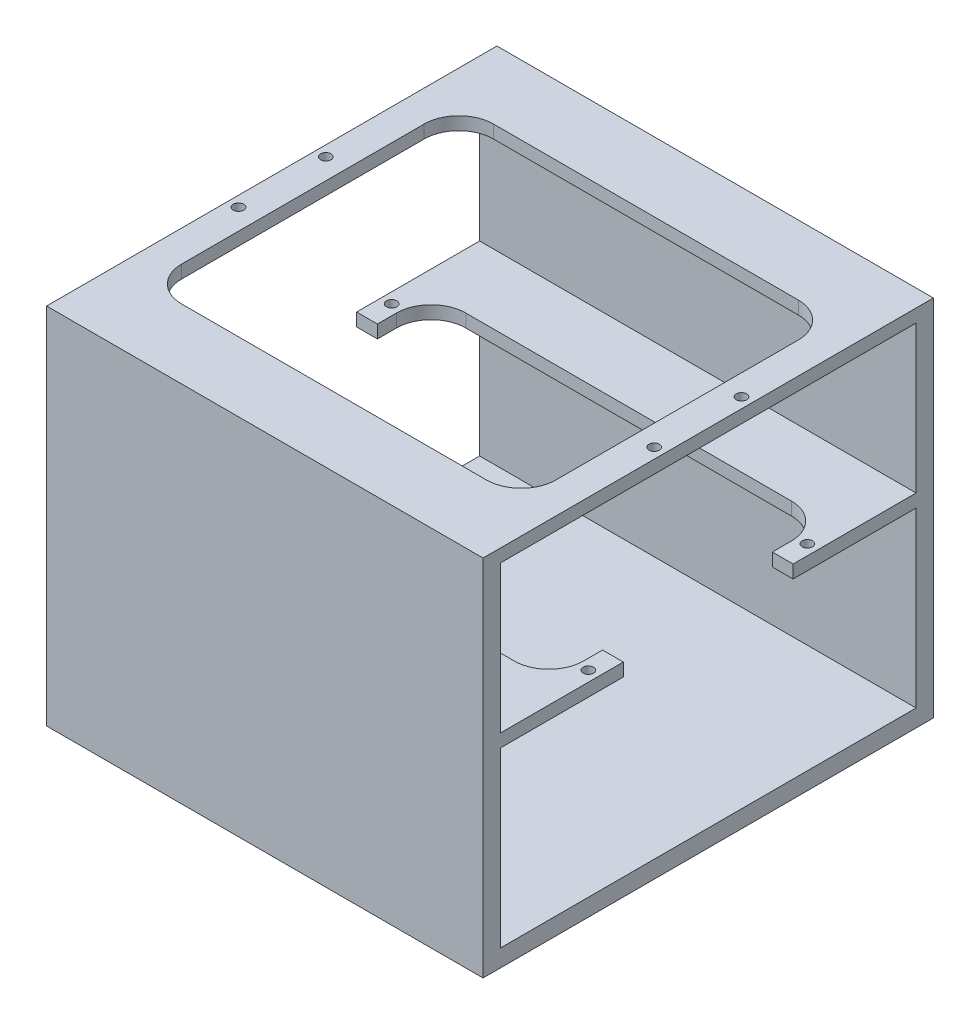
SolidWorks part; units mm, degrees
ref_plane "Front Plane" through (0, 0, 0) normal (0, 0, 1) x (1, 0, 0)
ref_plane "Top Plane" through (0, 0, 0) normal (0, 1, 0) x (1, 0, 0)
ref_plane "Right Plane" through (0, 0, 0) normal (1, 0, 0) x (0, 0, -1)
sketch "Sketch1" plane through (0, 0, 0) normal (1, 0, 0) x (0, 0, -1)
  line L0 (-95, 46.4295) -> (-95, -3.5705)
  line L1 (-43.5, 92.6795) -> (-95, 92.6795)
  line L3 (-43.5, 96.4295) -> (-100, 96.4295)
  line L4 (-100, 86.4295) -> (-100, 96.4295)
  line L5 (-100, 96.4295) -> (-90, 96.4295)
  line L6 (-100, 96.4295) -> (-100, -8.5705)
  line L7 (-100, -8.5705) -> (-90, -8.5705)
  line L8 (-95, 92.6795) -> (-95, 50.1795)
  line L9 (-95, 50.1795) -> (-59.5, 50.1795)
  line L11 (-95, 46.4295) -> (-59.5, 46.4295)
  line L12 (-59.5, 50.1795) -> (-59.5, 46.4295)
  line L13 (-90, -8.5705) -> (-35, -8.5705)
  line L15 (-95, -3.5705) -> (-35, -3.5705)
  line L16 (-35, -8.5705) -> (-35, -3.5705)
  line L18 (-43.5, 96.4295) -> (-35, 96.4295)
  line L20 (-43.5, 92.6795) -> (-35, 92.6795)
  line L21 (-35, 96.4295) -> (-35, 92.6795)
  dimension "D1" = 3.75
  dimension "D2" = 56.5
  dimension "D3" = 5
  dimension "D4" = 105
  dimension "D5" = 55
  dimension "D6" = 3.75
  dimension "D8" = 5
  dimension "D9" = 65
extrude "Boss-Extrude1" add sketch "Sketch1" along normal blind 126 contours L13 L16 L15 L0 L11 L12 L9 L8 L1 L3 L4 L6 L7 region at (0, 21.4295, 96.2349)
sketch "Sketch2" plane through (0, 96.4295, 0) normal (0, 1, 0) x (1, 0, 0)
  line L0 (0, -35.75) -> (0, 35.75) construction
  line L1 (126, -35) -> (0, -35) construction
  circle A0 centre (3, -47.6) radius 1.5
  circle A1 centre (123, -47.6) radius 1.5
  point P6 (123, -48)
  dimension "D1" = 3
  dimension "D2" = 3
  dimension "D3" = 120
  dimension "D4" = 3
  dimension "D5" = 12.6
extrude "Cut-Extrude1" cut sketch "Sketch2" against normal up to surface (46.25 mm away) contours A1 | A0 up to face at (63, 50.1795, 77.25)
sketch "Sketch3" plane through (0, 50.1795, 0) normal (0, 1, 0) x (1, 0, 0)
  line L3 (126, -35) -> (126, -100) construction
  line L4 (0, -35.75) -> (0, 35.75) construction
  line L5 (126, -35) -> (0, -35) construction
  line L7 (6, -95) -> (6, -59.5)
  line L8 (6, -65) -> (6, -35)
  line L9 (16, -75) -> (110, -75)
  line L10 (120, -95) -> (120, -59.5)
  line L11 (120, -65) -> (120, -35)
  line L12 (6, -35) -> (120, -35)
  circle A0 centre (3, -66.6) radius 1.5
  circle A1 centre (123, -66.6) radius 1.5
  arc A3 (16, -75) -> (6, -65) centre (16, -65) cw
  arc A4 (110, -75) -> (120, -65) centre (110, -65) ccw
  circle A8 centre (3, -47.6) radius 1.5 construction
  point P4 (3, -47.2759)
  point P5 (123.0848, -60.1289)
  point P6 (97.4811, -22.7665)
  point P7 (130.4814, -52.7323)
  point P8 (0, 0)
  point P9 (3, -48)
  point P25 (122.9283, -48)
  point P28 (0, 0)
  point P29 (2.7505, -62.7572)
  dimension "D1" = 3
  dimension "D2" = 3
  dimension "D4" = 3
  dimension "D5" = 19
  dimension "D8" = 10
  dimension "D9" = 10
  dimension "D3" = 3
  dimension "D6" = 6
  dimension "D10" = 40
  dimension "D7" = 6
extrude "Cut-Extrude3" cut sketch "Sketch3" against normal up to surface (53.75 mm away) contours A0 | A1 | L11 L12 L8 A3 L9 A4 up to face at (63, -3.5705, 65)
ref_plane "Plane1" through (0, 0, 35) normal (0, 0, -1) x (-1, 0, 0)
mirror "Mirror2" about plane through (0, 0, 35) normal (0, 0, -1) of "Cut-Extrude1", "Cut-Extrude3", "Boss-Extrude1"
sketch "Sketch4" plane through (0, 96.4295, 0) normal (0, 1, 0) x (1, 0, 0)
  line L0 (9, -35) -> (9, -70)
  line L2 (19, -80) -> (106.9997, -80)
  line L3 (116.9997, -70) -> (116.9997, -35)
  line L4 (9, -35) -> (116.9997, -35)
  line L5 (63, -100) -> (62.9998, -80) construction
  line L6 (9, -35) -> (116.9997, -35)
  line L7 (126, -100) -> (0, -100) construction
  line L9 (126, -35) -> (0, -35) construction
  line L10 (126, -100) -> (126, 30) construction
  line L11 (0, -57.75) -> (0, 57.75) construction
  line L12 (55, -35) -> (-55, -35) construction
  circle A0 centre (3, -47.6) radius 1.5 construction
  arc A2 (106.9997, -80) -> (116.9997, -70) centre (106.9997, -70) ccw
  arc A3 (19, -80) -> (9, -70) centre (19, -70) cw
  dimension "D1" = 6
  dimension "D4" = 10
  dimension "D2" = 45
extrude "Cut-Extrude6" cut sketch "Sketch4" against normal up to surface (46.25 mm away) contours L4 L3 A2 L2 A3 L0 up to face at (3, 50.1795, 68.1)
mirror "Mirror5" about plane through (0, 0, 35) normal (0, 0, -1) of "Cut-Extrude6"
